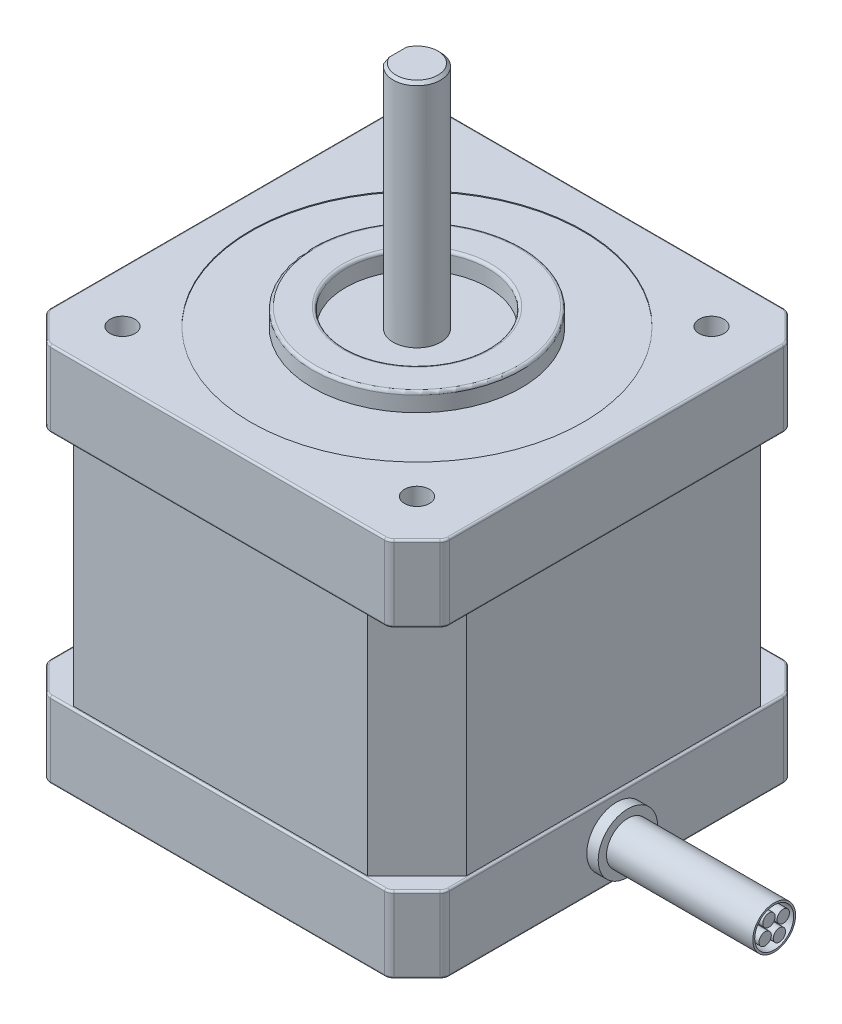
SolidWorks part; units mm, degrees
ref_plane "前视基准面" through (0, 0, 0) normal (0, 0, 1) x (1, 0, 0)
ref_plane "上视基准面" through (0, 0, 0) normal (0, 1, 0) x (1, 0, 0)
ref_plane "右视基准面" through (0, 0, 0) normal (1, 0, 0) x (0, 0, -1)
sketch "草图13" plane through (0, 0, 0) normal (0, 0, 1) x (1, 0, 0)
  line L0 (0, 0) -> (0, 40) construction
  dimension "L" = 40
sketch "草图1" plane through (0, 0, 0) normal (0, 1, 0) x (1, 0, 0)
  line L0 (0, 21) -> (0, -21) construction
  line L1 (-21, 21) -> (21, 21)
  line L2 (-21, 21) -> (-21, -21)
  line L3 (-21, -21) -> (21, -21)
  line L4 (21, 21) -> (21, -21)
  line L5 (-21, 0) -> (21, 0) construction
  dimension "D2" = 21
  dimension "W2" = 42
  dimension "D4" = 21
extrude "凸台-拉伸1" add sketch "草图1" along normal blind 40
chamfer "倒角3" distance 3 angle 45 4 edges at (21, 20, -21) (21, 20, 21) (-21, 20, 21) (-21, 20, -21)
sketch "草图2" plane through (0, 40, 0) normal (0, 1, 0) x (1, 0, 0)
  circle A0 centre (0, 0) radius 11
  dimension "E6" = 22
extrude "凸台-拉伸2" add sketch "草图2" along normal blind 1.8
ref_plane "基准面1" through (0, 8, 0) normal (0, -1, 0) x (1, 0, 0)
sketch "草图3" plane through (0, 40, 0) normal (0, 1, 0) x (1, 0, 0)
  line L0 (-2, 1.5) -> (-2, -1.5) construction
  circle A0 centre (0, 0) radius 2.5
  point P3 (2.5, 0)
  dimension "D1" = 4.5
  dimension "E4" = 5
extrude "凸台-拉伸3" add sketch "草图3" along normal blind 24
sketch "草图4" plane through (0, 8, 0) normal (0, -1, 0) x (1, 0, 0)
  line L0 (15.4716, 20.7) -> (-15.4716, 20.7)
  line L1 (-15.4716, 20.7) -> (-20.7, 15.4716)
  line L2 (-20.7, 15.4716) -> (-20.7, -15.4716)
  line L3 (-20.7, -15.4716) -> (-15.4716, -20.7)
  line L4 (-15.4716, -20.7) -> (15.4716, -20.7)
  line L5 (15.4716, -20.7) -> (20.7, -15.4716)
  line L6 (20.7, -15.4716) -> (20.7, 15.4716)
  line L7 (20.7, 15.4716) -> (15.4716, 20.7)
  line L8 (18, -21) -> (-18, -21) construction
  line L9 (-21, -18) -> (-21, 18) construction
  line L10 (21, 18) -> (21, -18) construction
  line L11 (-18, 21) -> (18, 21) construction
  line L15 (-18, 21) -> (-21, 18) construction
  line L21 (0, -21) -> (0, 21) construction
  line L22 (0, -21) -> (0, 21) construction
  line L23 (-21, 0) -> (21, 0) construction
  dimension "D1" = 0.3
  dimension "D2" = 0.3
  dimension "D3" = 0.3
  dimension "D4" = 0.3
  dimension "D5" = 2
extrude "切除-拉伸1" cut sketch "草图4" against normal blind 24 flip side to cut
fillet "圆角2" radius 1 16 edges at (21, 4, 18) (18, 4, 21) (-18, 4, 21) (-21, 4, 18) (21, 4, -18) (18, 4, -21) (-18, 4, -21) (-21, 4, -18) (-18, 36, -21) (-21, 36, -18) (21, 36, -18) (18, 36, -21) (21, 36, 18) (18, 36, 21) (-18, 36, 21) (-21, 36, 18)
fillet "圆角3" radius 0.2 64 edges at (-21, 32, 0) (-20.9239, 32, 17.9685) (0, 32, 21) (-17.9685, 32, 20.9239) (0, 8, 21) (17.9685, 8, 20.9239) (21, 8, 0) (20.9239, 8, 17.9685) (17.9685, 32, 20.9239) (21, 32, 0) (20.9239, 32, 17.9685) (-21, 8, 0) (-20.9239, 8, 17.9685) (-17.9685, 8, 20.9239) (0, 8, -21) (-17.9685, 8, -20.9239) (-20.9239, 8, -17.9685) (0, 32, -21) (-17.9685, 32, -20.9239) (-20.9239, 32, -17.9685) (-20.9239, 40, -17.9685) (-19.5, 40, -19.5) (-17.9685, 40, -20.9239) (0, 40, -21) (17.9685, 40, -20.9239) (19.5, 40, -19.5) (20.9239, 40, -17.9685) (21, 40, 0) (20.9239, 40, 17.9685) (19.5, 40, 19.5) (17.9685, 40, 20.9239) (0, 40, 21) (-17.9685, 40, 20.9239) (-20.9239, 40, 17.9685) (-20.9239, 0, -17.9685) (-21, 0, 0) (-20.9239, 0, 17.9685) (-19.5, 0, 19.5) (-17.9685, 0, 20.9239) (0, 0, 21) (17.9685, 0, 20.9239) (19.5, 0, 19.5) (20.9239, 0, 17.9685) (21, 0, 0) (20.9239, 0, -17.9685) (19.5, 0, -19.5) (17.9685, 0, -20.9239) (0, 0, -21) (-17.9685, 0, -20.9239) (-19.5, 40, 19.5) (-19.5, 32, 19.5) (19.5, 8, 19.5) (19.5, 32, 19.5) (-19.5, 8, 19.5) (-19.5, 8, -19.5) (-19.5, 32, -19.5) (-21, 40, 0) (-19.5, 0, -19.5) (17.9685, 8, -20.9239) (19.5, 8, -19.5) (20.9239, 8, -17.9685) (17.9685, 32, -20.9239) (19.5, 32, -19.5) (20.9239, 32, -17.9685)
sketch "草图14" plane through (0, 64, 0) normal (0, 1, 0) x (1, 0, 0)
  line L0 (-2, 1.5) -> (-2, -1.5) construction
  line L1 (-2, 1.5) -> (-2, -1.5)
  circle A1 centre (0, 0) radius 2.5 construction
  arc A2 (-2, 1.5) -> (-2, -1.5) centre (0, 0) ccw
extrude "切除-拉伸5" cut sketch "草图14" against normal blind 15
chamfer "倒角5" distance 0.3 angle 45 1 edges at (2.5, 64, 0)
chamfer "倒角4" distance 0.5 angle 45 1 edges at (-2, 49, 0)
chamfer "倒角6" [suppressed] distance 1 angle 45
sketch "草图6" plane through (0, 40, 0) normal (0, 1, 0) x (1, 0, 0)
  line L0 (0, 21) -> (0, -21) construction
  line L3 (-21, 0) -> (21, 0) construction
  line L7 (-21, -21) -> (21, -21) construction
  circle A0 centre (-15.5, 15.5) radius 1.3105
  circle A1 centre (15.5, 15.5) radius 1.3105
  circle A2 centre (15.5, -15.5) radius 1.3105
  circle A3 centre (-15.5, -15.5) radius 1.3105
  dimension "D1" = 31
  dimension "E2" = 2.621
  dimension "E1" = 15.5
extrude "切除-拉伸2" cut sketch "草图6" against normal blind 4.5
cosmetic thread "装饰螺纹线1" parameters "D2"=3
cosmetic thread "装饰螺纹线2" parameters "D2"=3
cosmetic thread "装饰螺纹线3" parameters "D2"=3
cosmetic thread "装饰螺纹线4" parameters "D2"=3
sketch "草图7" plane through (0, 41.8, 0) normal (0, 1, 0) x (1, 0, 0)
  circle A0 centre (0, 0) radius 7.5
  circle A1 centre (0, 0) radius 2.5
  dimension "D1" = 15
  dimension "D2" = 5
extrude "切除-拉伸3" cut sketch "草图7" against normal blind 2
sketch "草图8" plane through (21, 0, 0) normal (1, 0, 0) x (0, 0, -1)
  line L0 (0, 8) -> (0, 0) construction
  line L2 (-15.1716, 8) -> (-18, 8) construction
  circle A0 centre (0, 4) radius 3.125
  dimension "D1" = 6.25
extrude "凸台-拉伸5" add sketch "草图8" along normal blind 1.2
sketch "草图9" plane through (22.2, 0, 0) normal (1, 0, 0) x (0, 0, -1)
  circle A0 centre (0, 4) radius 2.25
  circle A1 centre (0, 4) radius 2.05
  circle A2 centre (0, 4) radius 3.125 construction
  dimension "D1" = 4.5
  dimension "D2" = 0.2
extrude "凸台-拉伸6" add sketch "草图9" along normal blind 15.4
sketch "草图10" plane through (22.2, 0, 0) normal (1, 0, 0) x (0, 0, -1)
  line L0 (0, 4) -> (-0.9526, 4.55) construction
  line L1 (0, 4) -> (0.9526, 4.55) construction
  line L2 (0, 4) -> (0, 2.9) construction
  circle A0 centre (-0.9526, 4.55) radius 0.65 construction
  circle A1 centre (0.9526, 4.55) radius 0.65
  circle A2 centre (0, 2.9) radius 0.65 construction
  circle A5 centre (0, 4) radius 1.1 construction
  dimension "D1" = 120
  dimension "D2" = 2.2
  dimension "D3" = 1.3
  dimension "D4" = 120
extrude "凸台-拉伸8" add sketch "草图10" along normal blind 15.4 contours A0 | A2 | A1
sketch "草图15" plane through (0, 40, 0) normal (0, 1, 0) x (1, 0, 0)
  circle A0 centre (0, 0) radius 17.5
  circle A1 centre (0, 0) radius 11 construction
  circle A2 centre (0, 0) radius 11
  dimension "D1" = 35
extrude "切除-拉伸6" cut sketch "草图15" against normal blind 0.1
fillet "圆角4" radius 0.3 2 edges at (0, 41.8, 7.5) (0, 41.8, 11)
pattern_circular "阵列(圆周)3" count 4 over 360 about axis through (0, 4, 0) along (1, 0, 0) of "凸台-拉伸8"
sketch "草图16" [suppressed] plane through (0, 0, -20.85) normal (0, 0, -1) x (-1, 0, 0)
  line L0 (0, 36.8) -> (0, 9.2) construction
  line L1 (15.6216, 36.8) -> (-15.6216, 36.8) construction
  line L2 (15.6216, 9.2) -> (-15.6216, 9.2) construction
  line L4 (-12.5, 7.2) -> (12.5, 7.2)
  line L5 (-12.5, 7.2) -> (-12.5, 38.8)
  line L6 (-12.5, 38.8) -> (12.5, 38.8)
  line L7 (12.5, 7.2) -> (12.5, 38.8)
  line L8 (-12.5, 7.2) -> (12.5, 38.8) construction
  line L9 (-12.5, 38.8) -> (12.5, 7.2) construction
  point P6 (0, 23)
  dimension "D1" = 2
  dimension "D2" = 25
extrude "切除-拉伸9" [suppressed] cut sketch "草图16" along normal blind 0.3
sketch "草图17" [suppressed] plane through (0, 0, 20.85) normal (0, 0, 1) x (1, 0, 0)
  line L4 (-12.5, 7.2) -> (12.5, 7.2)
  line L5 (-12.5, 38.8) -> (-12.5, 7.2)
  line L6 (12.5, 38.8) -> (-12.5, 38.8)
  line L7 (12.5, 7.2) -> (12.5, 38.8)
  line L8 (-12.5, 7.2) -> (12.5, 7.2)
  line L9 (-12.5, 38.8) -> (-12.5, 7.2)
  line L10 (12.5, 38.8) -> (-12.5, 38.8)
  line L11 (12.5, 7.2) -> (12.5, 38.8)
  dimension "D1" = 0
extrude "切除-拉伸10" [suppressed] cut sketch "草图17" along normal up to surface (0.3 mm away)
sketch "草图18" [suppressed] plane through (20.85, 0, 0) normal (1, 0, 0) x (0, 0, -1)
  line L0 (0, 9.2) -> (0, 36.8) construction
  line L1 (15.6216, 9.2) -> (-15.6216, 9.2) construction
  line L2 (15.6216, 36.8) -> (-15.6216, 36.8) construction
  line L4 (-12.5, 8.2) -> (12.5, 8.2)
  line L5 (-12.5, 8.2) -> (-12.5, 37.8)
  line L6 (-12.5, 37.8) -> (12.5, 37.8)
  line L7 (12.5, 8.2) -> (12.5, 37.8)
  line L8 (-12.5, 8.2) -> (12.5, 37.8) construction
  line L9 (-12.5, 37.8) -> (12.5, 8.2) construction
  point P6 (0, 23)
  dimension "D1" = 1
  dimension "D2" = 25
extrude "切除-拉伸11" [suppressed] cut sketch "草图18" along normal up to surface (0.3 mm away)
sketch "草图19" [suppressed] plane through (-20.85, 0, 0) normal (-1, 0, 0) x (0, 0, 1)
  line L4 (-12.5, 8.2) -> (12.5, 8.2)
  line L5 (-12.5, 37.8) -> (-12.5, 8.2)
  line L6 (12.5, 37.8) -> (-12.5, 37.8)
  line L7 (12.5, 8.2) -> (12.5, 37.8)
  line L8 (-12.5, 8.2) -> (12.5, 8.2)
  line L9 (-12.5, 37.8) -> (-12.5, 8.2)
  line L10 (12.5, 37.8) -> (-12.5, 37.8)
  line L11 (12.5, 8.2) -> (12.5, 37.8)
  dimension "D1" = 0
extrude "切除-拉伸12" [suppressed] cut sketch "草图19" along normal up to surface (0.3 mm away)
